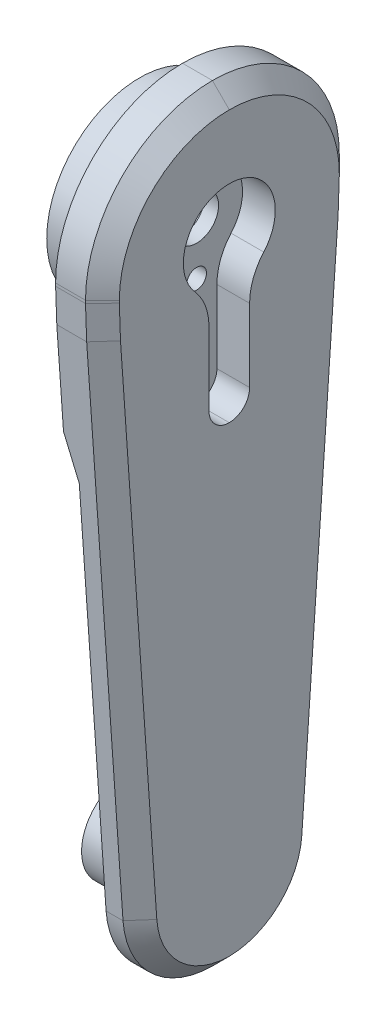
SolidWorks part; units mm, degrees
ref_plane "Front Plane" through (0, 0, 0) normal (0, 0, 1) x (1, 0, 0)
ref_plane "Top Plane" through (0, 0, 0) normal (0, 1, 0) x (1, 0, 0)
ref_plane "Right Plane" through (0, 0, 0) normal (1, 0, 0) x (0, 0, -1)
sketch "Sketch1" plane through (0, 0, 0) normal (1, 0, 0) x (0, 0, -1)
  line L1 (-10, 10) -> (10, 10)
  line L2 (-10, 10) -> (-10, -10)
  line L3 (-10, -10) -> (10, -10)
  line L4 (10, 10) -> (10, -10)
  line L5 (-10, 10) -> (10, -10) construction
  line L6 (-10, -10) -> (10, 10) construction
  point P0 (0, 0)
  dimension "D1" = 20
  dimension "D2" = 20
extrude "Boss-Extrude1" add sketch "Sketch1" along normal blind 20
sketch "Sketch2" plane through (20, 0, 0) normal (1, 0, 0) x (0, 0, -1)
  line L1 (-22.5, 35) -> (22.5, 35)
  line L2 (-22.5, 35) -> (-22.5, -35)
  line L3 (-22.5, -35) -> (22.5, -35)
  line L4 (22.5, 35) -> (22.5, -35)
  line L5 (-22.5, 35) -> (22.5, -35) construction
  line L6 (-22.5, -35) -> (22.5, 35) construction
  point P0 (0, 0)
  dimension "D1" = 45
  dimension "D2" = 70
extrude "Boss-Extrude2" add sketch "Sketch2" along normal blind 8.3
sketch "Sketch4" plane through (28.3, 0, 0) normal (1, 0, 0) x (0, 0, -1)
  line L0 (0, 7.65) -> (0, 8.1702) construction
  line L1 (7.65, 7.65) -> (-7.65, 7.65) construction
  line L17 (3.6, -26.55) -> (-3.6, -26.55) construction
  line L18 (-7.65, 7.65) -> (7.65, 7.65) construction
  line L22 (-7.65, 7.65) -> (-7.65, -27.55) construction
  line L23 (-7.65, -27.55) -> (7.65, -27.55) construction
  line L24 (7.65, 7.65) -> (7.65, -27.55) construction
  line L25 (-7.65, 7.65) -> (7.65, -27.55) construction
  line L26 (-7.65, -27.55) -> (7.65, 7.65) construction
  line L27 (3.6, -26.55) -> (3.6, -28.55) construction
  line L28 (3.6, -28.55) -> (-3.6, -28.55) construction
  line L29 (-3.6, -26.55) -> (-3.6, -28.55) construction
  line L30 (3.6, -26.55) -> (-3.6, -28.55) construction
  line L31 (3.6, -28.55) -> (-3.6, -26.55) construction
  line L34 (3.6, -28.55) -> (-3.6, -28.55)
  line L35 (-3.6, -28.55) -> (-3.6, -7.3118)
  line L36 (3.6, -28.55) -> (3.6, -7.3118)
  arc A1 (3.6, -6.75) -> (-3.6, -6.75) centre (0, 0) ccw construction
  arc A2 (3.6, -7.3118) -> (-3.6, -7.3118) centre (0, 0) ccw
  point P1 (0, -27.55)
  point P7 (0, -13.75)
  point P10 (0, 7.65)
  point P14 (0, -9.95)
  dimension "D1" = 15.3
  dimension "D5" = 2
  dimension "D2" = 15.3
  dimension "D3" = 35.2
  dimension "D4" = 7.2
extrude "Cut-Extrude1" cut sketch "Sketch4" against normal blind 5.8
fillet "Fillet1" radius 3.6 2 edges at (25.4, -28.55, 3.6) (25.4, -28.55, -3.6)
fillet "Fillet2" radius 10 2 edges at (25.4, -7.3118, 3.6) (25.4, -7.3118, -3.6)
sketch "Sketch5" plane through (0, 0, 0) normal (-1, 0, 0) x (0, 0, 1)
  circle A0 centre (0, 0) radius 3.9
  dimension "D1" = 7.8
extrude "Cut-Extrude2" cut sketch "Sketch5" against normal through all
sketch "Sketch6" plane through (22.5, 0, 0) normal (1, 0, 0) x (0, 0, -1)
  line L0 (0, -19.35) -> (0, 0) construction
  line L1 (0, -25.65) -> (0, -23.15) construction
  line L2 (0, -23.15) -> (0, -21.85) construction
  line L3 (0, -21.85) -> (0, -19.35) construction
  line L5 (0, 0) -> (1.164, 0) construction
  line L6 (0, 0) -> (0, -9.35) construction
  line L7 (0, -9.35) -> (1.164, -9.35) construction
  line L8 (1.164, 0) -> (1.164, -9.35) construction
  line L9 (0, 0) -> (1.164, -9.35) construction
  line L10 (0, -9.35) -> (1.164, 0) construction
  circle A0 centre (0, -20.6) radius 1.75
  circle A1 centre (0, -9.35) radius 1.75
  point P11 (0.582, -4.675)
  dimension "D5" = 3.5
  dimension "D6" = 9.35
  dimension "D7" = 3.5
  dimension "D1" = 19.35
  dimension "D2" = 2.5
  dimension "D3" = 1.3
  dimension "D4" = 2.5
extrude "Cut-Extrude3" cut sketch "Sketch6" against normal up to next
sketch "Sketch13" plane through (0, 0, 0) normal (-1, 0, 0) x (0, 0, 1)
  line L1 (-10, 10) -> (10, 10)
  line L2 (-10, 10) -> (-10, -10)
  line L3 (-10, -10) -> (10, -10)
  line L4 (10, 10) -> (10, -10)
extrude "Cut-Extrude9" cut sketch "Sketch13" against normal up to surface (20 mm away) up to face at (20, -20.6, -1.75)
sketch "Sketch14" plane through (20, 0, 0) normal (-1, 0, 0) x (0, 0, 1)
  line L0 (0, -11.1) -> (0, -18.85) construction
  circle A0 centre (0, -9.35) radius 1.75 construction
  circle A1 centre (0, -20.6) radius 1.75 construction
  circle A3 centre (0, 0) radius 16.475
  circle A4 centre (0, 0) radius 3.9 construction
  point P7 (0, -14.975)
  dimension "D1" = 32.95
  dimension "D2" = 12.575
extrude "Boss-Extrude3" add sketch "Sketch14" along normal blind 7.6 contours A3
sketch "Sketch15" plane through (0, 35, 0) normal (0, 1, 0) x (1, 0, 0)
  line L1 (20, 22.5) -> (28.3, 22.5)
  line L2 (20, 22.5) -> (20, -22.5)
  line L3 (20, -22.5) -> (28.3, -22.5)
  line L4 (28.3, 22.5) -> (28.3, -22.5)
extrude "Cut-Extrude10" cut sketch "Sketch15" against normal blind 12.5
sketch "Sketch16" plane through (12.4, 0, 0) normal (-1, 0, 0) x (0, 0, 1)
  circle A4 centre (0, 0) radius 13.475
  circle A5 centre (0, 0) radius 13.475
  dimension "D1" = 3
extrude "Cut-Extrude11" cut sketch "Sketch16" against normal blind 7.6
sketch "Sketch17" plane through (20, 0, 0) normal (-1, 0, 0) x (0, 0, 1)
  line L0 (0, 0) -> (-22.5, 0) construction
  line L1 (-22.5, -35) -> (-22.5, 22.5) construction
  line L2 (0, 0) -> (22.5, 0) construction
  line L3 (22.5, 22.5) -> (22.5, -35) construction
  line L4 (0, 0) -> (0, 22.5) construction
  line L5 (-22.5, 22.5) -> (22.5, 22.5) construction
  point P5 (0, 0)
sketch "Sketch18" plane through (0, -35, 0) normal (0, -1, 0) x (1, 0, 0)
  line L0 (20, 0) -> (20, 22.5) construction
  line L1 (20, 22.5) -> (28.3, 22.5)
  line L2 (20, 22.5) -> (20, -22.5)
  line L3 (20, -22.5) -> (28.3, -22.5)
  line L4 (28.3, 22.5) -> (28.3, -22.5)
  line L5 (28.3, 22.5) -> (20, 22.5) construction
  line L6 (28.3, 22.5) -> (28.3, -22.5) construction
extrude "Boss-Extrude4" add sketch "Sketch18" along normal blind 78.5
sketch "Sketch20" plane through (20, 0, 0) normal (-1, 0, 0) x (0, 0, 1)
  line L0 (0, 0) -> (0, -100) construction
  line L1 (22.5, 22.5) -> (22.5, -113.5) construction
  line L2 (-22.5, -113.5) -> (22.5, -113.5)
  line L3 (-22.5, -113.5) -> (-22.5, -33.5)
  line L4 (-22.5, -33.5) -> (22.5, -33.5)
  line L5 (22.5, -113.5) -> (22.5, -33.5)
  dimension "D1" = 100
  dimension "D2" = 80
fillet "Fillet5" radius 22.5 2 edges at (24.15, 22.5, -22.5) (24.15, 22.5, 22.5)
extrude "Cut-Extrude12" cut sketch "Sketch20" against normal blind 2.3
sketch "Sketch21" plane through (22.3, 0, 0) normal (-1, 0, 0) x (0, 0, 1)
  line L0 (0, -113.5) -> (0, -99.5) construction
  line L1 (-22.5, -113.5) -> (22.5, -113.5) construction
  circle A0 centre (0, -99.5) radius 8
  dimension "D2" = 16
  dimension "D1" = 14
extrude "Boss-Extrude5" add sketch "Sketch21" along normal blind 12.2
chamfer "Chamfer1" distance 10 angle 18 1 edges at (20, -33.5, 0) first distance on face at (20, -20.6, -1.75)
chamfer "Chamfer2" distance 110 angle 4 2 edges at (25.3, -113.5, -22.5) (25.3, -113.5, 22.5) first distance on face at (23.5333, -46.8464, -22.5) first distance on face at (23.5333, -46.8464, 22.5)
chamfer "Chamfer3" distance 3 angle 2 2 edges at (24.15, -3.5, 22.5) (24.15, -3.5, -22.5) first distance on face at (23.5333, -48.0131, 19.3873) first distance on face at (23.5333, -48.0131, -19.3873)
fillet "Fillet6" radius 16 2 edges at (25.3, -113.5, -14.8081) (25.3, -113.5, 14.8081)
chamfer "Chamfer4" distance 3 angle 45 10 edges at (28.3, -3.4963, -22.3954) (28.3, -0.25, -22.5) (28.3, 15.9099, -15.9099) (28.3, 15.9099, 15.9099) (28.3, -0.25, 22.5) (28.3, -3.4963, 22.3954) (28.3, -52.5544, 19.0698) (28.3, -109.1633, 10.8407) (28.3, -109.1633, -10.8407) (28.3, -52.5544, -19.0698)
sketch "Sketch23" plane through (10.1, 0, 0) normal (-1, 0, 0) x (0, 0, 1)
  line L0 (0, -99.5) -> (-8, -99.5) construction
  line L1 (0, -99.5) -> (8, -99.5) construction
  line L2 (-6.35, -99.5) -> (-8, -99.5)
  circle A0 centre (0, -99.5) radius 8 construction
  circle A1 centre (-4, -99.5) radius 2.35
  circle A2 centre (4, -99.5) radius 2.35
  point P0 (0, -99.5)
  dimension "D1" = 4.7
  dimension "D2" = 4.7
extrude "Cut-Extrude13" cut sketch "Sketch23" against normal blind 8 contours A2 | A1
chamfer "Chamfer5" distance 1 angle 45 2 edges at (10.1, -99.5, 6.35) (10.1, -99.5, -1.65)
sketch "Sketch24" plane through (20, 0, 0) normal (-1, 0, 0) x (0, 0, 1)
  line L0 (0, 0) -> (0, 13.475) construction
  line L1 (-16.475, 0) -> (-5.975, 0) construction
  line L3 (3.9, 0) -> (16.475, 0) construction
  circle A0 centre (0, 0) radius 3.9 construction
  circle A4 centre (0, 0) radius 16.475 construction
  circle A5 centre (-11.225, 0) radius 5
  circle A6 centre (0, 0) radius 13.475 construction
  circle A7 centre (11.225, 0) radius 5
  dimension "D1" = 10.5
  dimension "D2" = 10
extrude "Boss-Extrude6" add sketch "Sketch24" along normal up to surface (7.6 mm away) up to face at (12.4, 0, 13.475)
fillet "Fillet8" radius 2 4 edges at (16.2, 4.8109, -12.5869) (16.2, -4.8109, -12.5869) (16.2, -4.8109, 12.5869) (16.2, 4.8109, 12.5869)
fillet "Fillet9" radius 1.5 8 edges at (20, 6.076, 11.1856) (20, 0, 6.225) (20, -6.076, 11.1856) (20, -13.475, 0) (20, -6.076, -11.1856) (20, 0, -6.225) (20, 6.076, -11.1856) (20, 13.475, 0)
sketch "Sketch27" plane through (12.4, 0, 0) normal (-1, 0, 0) x (0, 0, 1)
  line L0 (-16.475, 0) -> (-5.975, 0) construction
  line L1 (0, 0) -> (-22.5, 0) construction
  line L2 (0, 0) -> (0, 5.9787) construction
  line L3 (0, 0) -> (0, 22.5) construction
  circle A0 centre (0, 0) radius 16.475 construction
  circle A1 centre (-11.225, 0) radius 2.35
  circle A2 centre (11.225, 0) radius 2.35
  dimension "D2" = 4.7
  dimension "D1" = 10.5
extrude "Cut-Extrude14" cut sketch "Sketch27" against normal blind 8 contours A1 | A2
chamfer "Chamfer6" distance 1 angle 45 2 edges at (12.4, 0, -8.875) (12.4, 0, 8.875)
ref_plane "Plane1" through (28.3, -5.3971, 6.1069) normal (-1, 0, 0) x (0, 0, 1)
